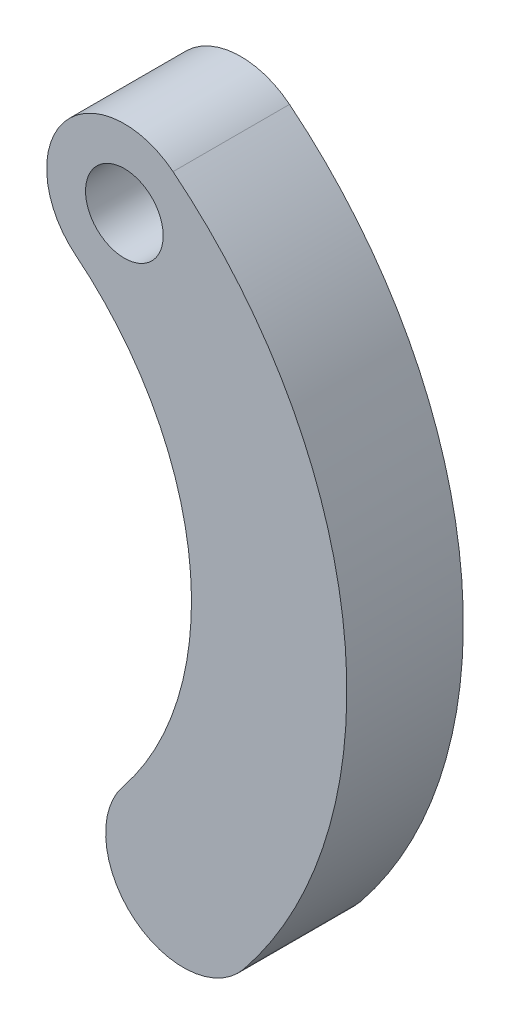
SolidWorks part; units mm, degrees
ref_plane "Front Plane" through (0, 0, 0) normal (0, 0, 1) x (1, 0, 0)
ref_plane "Top Plane" through (0, 0, 0) normal (0, 1, 0) x (1, 0, 0)
ref_plane "Right Plane" through (0, 0, 0) normal (1, 0, 0) x (0, 0, -1)
sketch "Sketch1" plane through (0, 0, 0) normal (0, 0, 1) x (1, 0, 0)
  circle A0 centre (0, 9.5) radius 1
  arc A1 (0, 9.5) -> (1.5186, -4.5604) centre (-6.2709, 1.7105) cw construction
  arc A2 (3.0765, -5.8145) -> (1.2542, 11.0579) centre (-6.2709, 1.7105) ccw
  arc A3 (-0.0393, -3.3062) -> (-1.2542, 7.9421) centre (-6.2709, 1.7105) ccw
  arc A4 (-0.0393, -3.3062) -> (3.0765, -5.8145) centre (1.5186, -4.5604) ccw
  arc A5 (1.2542, 11.0579) -> (-1.2542, 7.9421) centre (0, 9.5) ccw
  circle A6 centre (0, 0) radius 1.5 construction
  circle A7 centre (0, 9.5) radius 1 construction
  point P5 (3.6713, 2.7843)
  point P10 (4.5189, -3.9007)
  dimension "D1" = 4
  dimension "D3" = 10
  dimension "D2" = 90
extrude "Boss-Extrude1" add sketch "Sketch1" along normal blind 3
